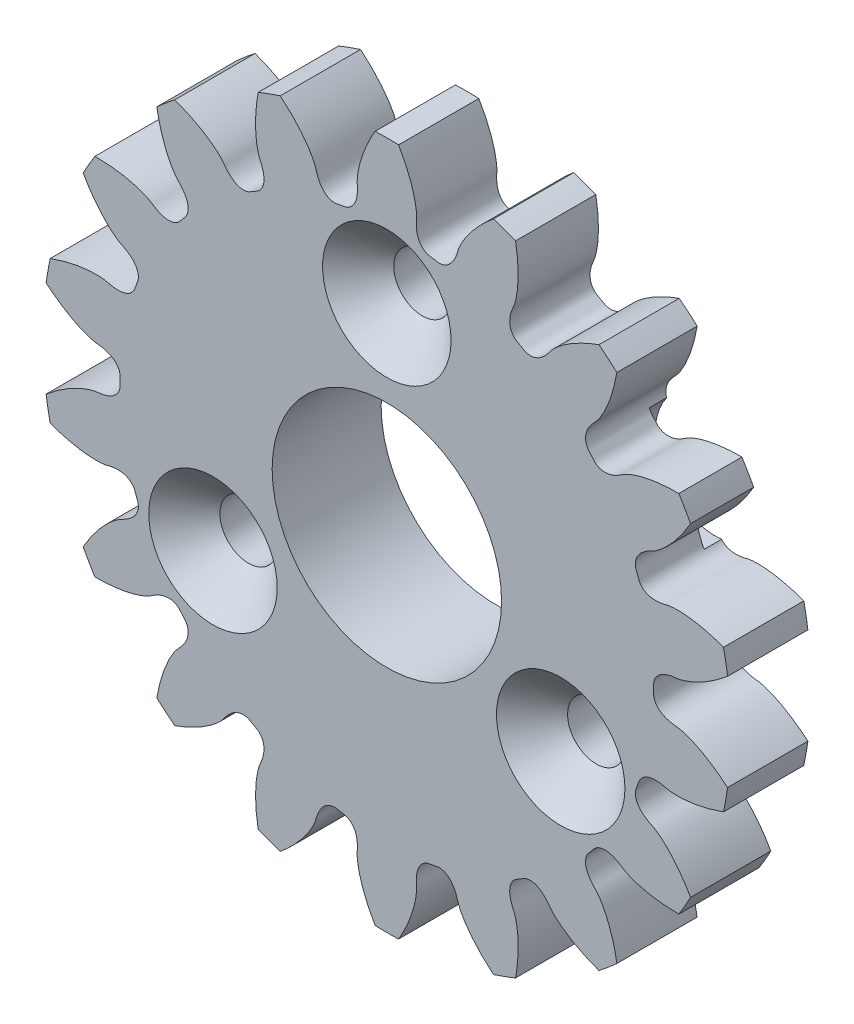
SolidWorks part; units mm, degrees
material "POM 乙缩醛共聚物"
ref_plane "前视基准面" through (0, 0, 0) normal (0, 0, 1) x (1, 0, 0)
ref_plane "上视基准面" through (0, 0, 0) normal (0, 1, 0) x (1, 0, 0)
ref_plane "右视基准面" through (0, 0, 0) normal (1, 0, 0) x (0, 0, -1)
ref_axis "基准轴1" through (0, 0, 55) along (0, 0, -1)
sketch "旋转草图小直齿轮" plane through (0, 0, 0) normal (1, 0, 0) x (0, 0, -1)
  line L0 (0, 0) -> (1, 0) construction
  line L1 (-3.5, 0) -> (-3.5, 30)
  line L2 (-3.5, 30) -> (3.5, 30)
  line L3 (3.5, 30) -> (3.5, 0)
  line L4 (3.5, 0) -> (-3.5, 0)
revolve "小直齿轮" add sketch "旋转草图小直齿轮" angle 360 about L0
sketch "齿草图小直齿轮" plane through (0, 0, 0) normal (0, 0, 1) x (1, 0, 0)
  arc A0 (29.8396, 4.3154) -> (29.8396, -4.3154) centre (0, 0) cw
  spline S0 degree 3 poles (29.8396, -4.3154) (29.4741, -3.9986) (28.9819, -3.6084) (28.3536, -3.1763) (28.0125, -2.9575) (27.687, -2.7631) (27.3784, -2.592) (27.0876, -2.4427) (26.8159, -2.3141) (26.5641, -2.2046) (26.3333, -2.1129) (26.1243, -2.0375) (25.9378, -1.9769) (25.7745, -1.9296) (25.6352, -1.8939) (25.5204, -1.8684) (25.4305, -1.8514) (25.3659, -1.8413) (25.327, -1.8363) (25.2504, -1.8293) (25.1586, -1.8222) (25.0438, -1.808) (24.9611, -1.7964) (24.8799, -1.7831) (24.8002, -1.7684) (24.7221, -1.7522) (24.6453, -1.7345) (24.57, -1.7151) (24.4961, -1.6942) (24.4235, -1.6716) (24.3522, -1.6473) (24.2822, -1.6211) (24.2134, -1.5931) (24.1457, -1.563) (24.0791, -1.5307) (24.0136, -1.4961) (23.9492, -1.459) (23.8857, -1.419) (23.8234, -1.376) (23.762, -1.3296) (23.7019, -1.2794) (23.6432, -1.2251) (23.586, -1.1662) (23.5308, -1.1024) (23.4781, -1.0331) (23.4285, -0.9581) (23.3828, -0.8772) (23.342, -0.7903) (23.3071, -0.6977) (23.2793, -0.5998) (23.2596, -0.4977) (23.2499, -0.4008) (23.2457, -0.2346) (23.2534, 0) (23.2457, 0.2346) (23.2499, 0.4008) (23.2596, 0.4977) (23.2793, 0.5998) (23.3071, 0.6977) (23.342, 0.7903) (23.3828, 0.8772) (23.4285, 0.9581) (23.4781, 1.0331) (23.5308, 1.1024) (23.586, 1.1662) (23.6432, 1.2251) (23.7019, 1.2794) (23.762, 1.3296) (23.8234, 1.376) (23.8857, 1.419) (23.9492, 1.459) (24.0136, 1.4961) (24.0791, 1.5307) (24.1457, 1.563) (24.2134, 1.5931) (24.2822, 1.6211) (24.3522, 1.6473) (24.4235, 1.6716) (24.4961, 1.6942) (24.57, 1.7151) (24.6453, 1.7345) (24.7221, 1.7522) (24.8002, 1.7684) (24.8799, 1.7831) (24.9611, 1.7964) (25.0438, 1.808) (25.1586, 1.8222) (25.2504, 1.8293) (25.327, 1.8363) (25.3659, 1.8413) (25.4305, 1.8514) (25.5204, 1.8684) (25.6352, 1.8939) (25.7745, 1.9296) (25.9378, 1.9769) (26.1243, 2.0375) (26.3333, 2.1129) (26.5641, 2.2046) (26.8159, 2.3141) (27.0876, 2.4427) (27.3784, 2.592) (27.687, 2.7631) (28.0125, 2.9575) (28.3536, 3.1763) (28.9819, 3.6084) (29.4741, 3.9986) (29.8396, 4.3154) knots 0 0 0 0 0.086682 0.112454 0.136665 0.159314 0.1804 0.199925 0.217888 0.234288 0.249127 0.262404 0.274119 0.284272 0.292862 0.299891 0.305358 0.309263 0.311606 0.312387 0.323046 0.328118 0.333109 0.338022 0.342862 0.347631 0.352335 0.356978 0.361567 0.366106 0.370604 0.375067 0.379505 0.383926 0.388341 0.392762 0.397202 0.401675 0.406197 0.410784 0.415455 0.420228 0.425122 0.430157 0.43535 0.440715 0.446262 0.451994 0.457907 0.463985 0.470202 0.476522 0.481419 0.5 0.518581 0.523478 0.529798 0.536015 0.542093 0.548006 0.553738 0.559285 0.56465 0.569843 0.574878 0.579772 0.584545 0.589216 0.593803 0.598325 0.602798 0.607238 0.611659 0.616074 0.620495 0.624933 0.629396 0.633894 0.638433 0.643022 0.647665 0.652369 0.657138 0.661978 0.666891 0.671882 0.676954 0.687613 0.688394 0.690737 0.694642 0.700109 0.707138 0.715728 0.725881 0.737596 0.750873 0.765712 0.782112 0.800075 0.8196 0.840686 0.863335 0.887546 0.913318 1 1 1 1
extrude "齿拉伸切除小直齿轮" cut sketch "齿草图小直齿轮" against normal blind 3.5 and the other way blind 3.5
pattern_circular "齿形小直齿轮" count 18 every 20 about axis through (0, 0, 55) along (0, 0, -1) of "齿拉伸切除小直齿轮"
sketch "孔旋转草图" plane through (0, 0, 0) normal (1, 0, 0) x (0, 0, -1)
  line L0 (0, 0) -> (1, 0) construction
  line L1 (-3.5, 0) -> (3.5, 0)
  line L2 (3.5, 0) -> (3.5, 6.35)
  line L3 (3.5, 6.35) -> (-3.5, 6.35)
  line L4 (-3.5, 6.35) -> (-3.5, 0)
  dimension "TaperSide1" = 6.35
  dimension "TaperSide2" = 6.35
revolve "孔旋转切除" cut sketch "孔旋转草图" angle 360 about L0
sketch "辅助草图小直齿轮" plane through (0, 0, 0) normal (0, 0, 1) x (1, 0, 0)
  circle A0 centre (0, 0) radius 27 construction
  circle A1 centre (0, 0) radius 25.3717 construction
  circle A2 centre (0, 0) radius 25.3717 construction
  circle A3 centre (0, 0) radius 30 construction
  circle A4 centre (0, 0) radius 23.25 construction
  dimension "PitchDiameter" = 54
  dimension "BaseDiameter" = 50.7434
  dimension "FormDiameter" = 50.7434
  dimension "MajorDiameter" = 60
  dimension "MinorDiameter" = 46.5
sketch "草图1" plane through (0, 0, 3.5) normal (0, 0, 1) x (1, 0, 0)
  circle A0 centre (0, 0) radius 17.5 construction
  circle A1 centre (0, 17.5) radius 2.5
  circle A2 centre (15.1554, -8.75) radius 2.5
  circle A3 centre (-15.1554, -8.75) radius 2.5
  point P14 (0, 0)
  dimension "D2" = 5
  dimension "D3" = 35
  dimension "D1" = 3
extrude "切除-拉伸1" cut sketch "草图1" against normal blind 10
sketch "草图5" plane through (0, 0, 3.5) normal (0, 0, 1) x (1, 0, 0)
  circle A0 centre (0, 0) radius 10
  dimension "D1" = 20
extrude "切除-拉伸2" cut sketch "草图5" against normal through all
sketch "草图6" plane through (0, 0, -3.5) normal (0, 0, -1) x (-1, 0, 0)
  circle A0 centre (0, 0) radius 10
  circle A1 centre (0, 0) radius 13
  circle A2 centre (0, 0) radius 10 construction
  dimension "D1" = 26
extrude "凸台-拉伸2" add sketch "草图6" along normal blind 2.5
sketch "草图7" plane through (0, 0, -3.5) normal (0, 0, -1) x (-1, 0, 0)
  circle A0 centre (0, -25) radius 5.25
  circle A1 centre (0, 0) radius 25 construction
  circle A2 centre (-21.6506, 12.5) radius 5.25
  circle A3 centre (21.6506, 12.5) radius 5.25
  point P12 (0, 0)
  dimension "D1" = 10.5
  dimension "D2" = 50
  dimension "D3" = 3
extrude "切除-拉伸3" cut sketch "草图7" against normal blind 1.5
hole_wizard "打孔尺寸(%根据十字)槽沉头木螺钉的类型2" positions "3D草图2" profile "草图8" countersink size "M5" standard "GB" end condition through all
sketch3d "3D草图2"
  line L0 (0, 17.5, -3.5) -> (0, 17.5, 3.5) construction
  line L1 (-15.1554, -8.75, -3.5) -> (-15.1554, -8.75, 3.5) construction
  line L2 (15.1554, -8.75, -3.5) -> (15.1554, -8.75, 3.5) construction
  point P0 (0, 17.5, 3.5)
  point P4 (-15.1554, -8.75, 3.5)
  point P8 (15.1554, -8.75, 3.5)
sketch "草图8" plane through (0, 17.5, 3.5) normal (1, 0, 0) x (0, -1, 0)
  line L0 (0, 0) -> (0, 9.5)
  line L1 (0, 9.5) -> (2.5, 9.5)
  line L2 (2.5, 9.5) -> (2.5, 3.1)
  line L3 (2.5, 3.1) -> (5.6, 0)
  line L5 (5.6, 0) -> (0, 0)
  line L6 (-2.5, 3.1) -> (-5.6, 0) construction
  line L11 (0, -6.35) -> (0, 107.95) construction
  dimension "通孔孔直径" = 5
  dimension "通孔孔深度" = 9.5
  dimension "近端锥形沉头孔直径" = 11.2
  dimension "近端锥形沉头孔角度" = 90
ref_plane "基准面1" through (0, 0, -2.6) normal (0, 0, 1) x (1, 0, 0)
sketch "草图10" plane through (0, 0, -2.6) normal (0, 0, 1) x (1, 0, 0)
  circle A0 centre (0, 0) radius 34
  circle A1 centre (0, 0) radius 30 construction
  circle A2 centre (21.6506, 12.5) radius 5.25
  arc A3 (17.3887, 15.5657) -> (22.1746, 7.2762) centre (21.6506, 12.5) ccw construction
  circle A4 centre (0, -25) radius 5.25
  circle A5 centre (-21.6506, 12.5) radius 5.25
  circle A6 centre (0, 0) radius 10 construction
  circle A7 centre (0, 0) radius 10
  point P18 (0, 0)
  dimension "D1" = 4
  dimension "D2" = 3
extrude "凸台-拉伸4" [suppressed] add sketch "草图10" along normal blind 1
